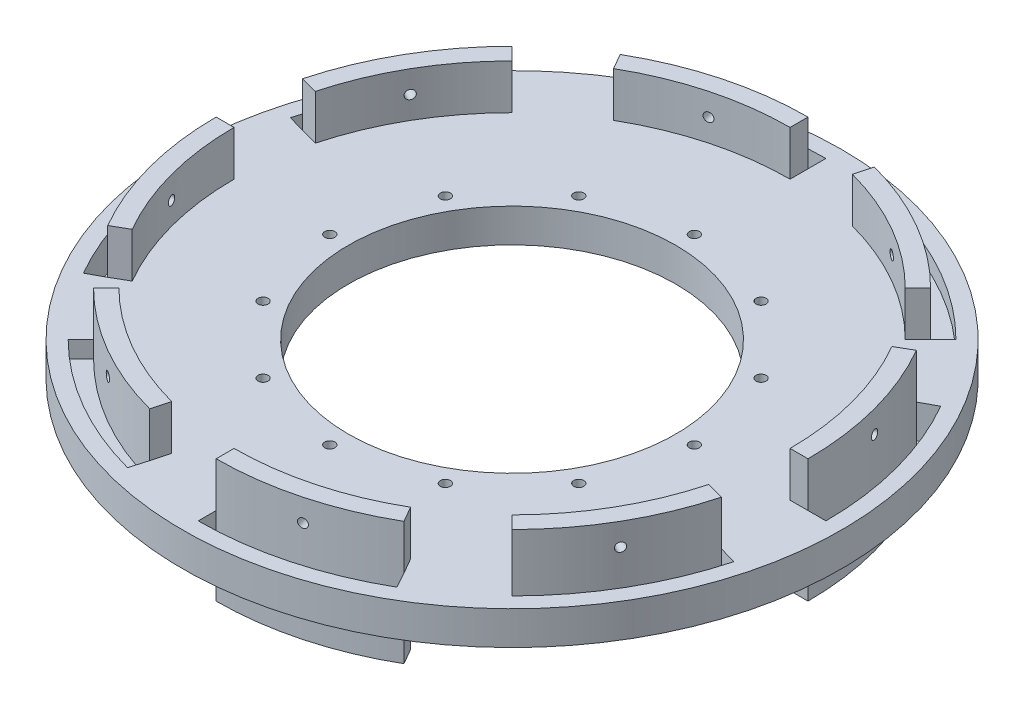
SolidWorks part; units mm, degrees
material "6061-T6 (SS)"
ref_plane "Front Plane" through (0, 0, 0) normal (0, 0, 1) x (1, 0, 0)
ref_plane "Top Plane" through (0, 0, 0) normal (0, 1, 0) x (1, 0, 0)
ref_plane "Right Plane" through (0, 0, 0) normal (1, 0, 0) x (0, 0, -1)
sketch "Sketch1" plane through (0, 0, 0) normal (0, 1, 0) x (1, 0, 0)
  line L5 (0, 0) -> (127.635, 0)
  line L6 (0, 0) -> (0, 127.635)
  line L7 (0, 127.635) -> (127.635, 127.635)
  line L8 (127.635, 0) -> (127.635, 127.635)
  dimension "D1" = 127.635
  dimension "D2" = 127.635
extrude "Boss-Extrude1" add sketch "Sketch1" along normal blind 9.525 contours L5 L8 L7 L6
sketch "Sketch12" plane through (0, 0, 0) normal (0, -1, 0) x (1, 0, 0)
  line L0 (63.8175, 0) -> (63.8175, -127.635) construction
  line L1 (0, 0) -> (127.635, 0) construction
  line L2 (0, -127.635) -> (127.635, -127.635) construction
  line L3 (0, -63.8175) -> (127.635, -63.8175) construction
  line L4 (0, 0) -> (0, -127.635) construction
  line L5 (127.635, 0) -> (127.635, -127.635) construction
  circle A0 centre (63.8175, -63.8175) radius 93.345
  dimension "D1" = 186.69
extrude "Boss-Extrude2" add sketch "Sketch12" against normal up to surface (9.525 mm away) contours A0 up to face at (63.8175, 9.525, -63.8175)
sketch "Sketch5" plane through (0, 9.525, 0) normal (0, 1, 0) x (1, 0, 0)
  circle A0 centre (63.8175, 63.8175) radius 46.355
  circle A3 centre (63.8175, 63.8175) radius 93.345 construction
  dimension "D1" = 92.71
extrude "Cut-Extrude1" cut sketch "Sketch5" against normal blind 9.525
sketch "Sketch11" plane through (0, 9.525, 0) normal (0, 1, 0) x (1, 0, 0)
  line L0 (63.8175, 63.8175) -> (63.8175, 115.443) construction
  circle A0 centre (63.8175, 115.443) radius 1.4351
  dimension "D2" = 2.8702
  dimension "D1" = 51.6255
extrude "Cut-Extrude3" cut sketch "Sketch11" against normal through all contours A0
pattern_circular "CirPattern1" count 12 over 360 about axis through (63.8175, 9.525, -63.8175) along (0, 1, 0) of "Cut-Extrude3"
sketch "Sketch14" plane through (0, 9.525, 0) normal (0, -1, 0) x (1, 0, 0)
  line L0 (63.8175, -63.8175) -> (147.6375, -63.8175) construction
  line L1 (0, -5.2388) -> (0, 5.2388) construction
  line L2 (147.6375, -63.8175) -> (152.7175, -63.8175)
  line L3 (136.3808, -105.7742) -> (140.8401, -108.2104)
  circle A0 centre (63.8175, -63.8175) radius 46.355 construction
  arc A2 (147.6375, -63.8175) -> (136.3808, -105.7742) centre (63.8175, -63.8175) cw
  arc A3 (152.7175, -63.8175) -> (140.8401, -108.2104) centre (63.8175, -63.8175) cw
  point P0 (63.8175, -63.8175)
  dimension "D1" = 83.82
  dimension "D2" = 88.9
  dimension "D3" = 46.482
  dimension "D4" = 43.942
extrude "Bottom support hole" cut sketch "Sketch14" along normal blind 4.7625
sketch "Sketch15" plane through (0, 9.525, 0) normal (0, -1, 0) x (1, 0, 0)
  line L0 (63.8175, -63.8175) -> (147.6375, -63.8175) construction
  line L2 (142.5575, -63.8175) -> (147.6375, -63.8175)
  line L3 (131.983, -103.2314) -> (136.3808, -105.7742)
  arc A2 (142.5575, -63.8175) -> (131.983, -103.2314) centre (63.8175, -63.8175) cw
  arc A3 (147.6375, -63.8175) -> (136.3808, -105.7742) centre (63.8175, -63.8175) cw
  dimension "D1" = 43.942
  dimension "D3" = 78.74
extrude "Bottom support guide" add sketch "Sketch15" against normal blind 12.7
ref_plane "Bottom support bolt hole plane" through (153.6961, 0, -41.2358) normal (0.9658, 0, -0.2591) x (-0.2591, 0, -0.9658)
sketch "Sketch16" plane through (153.6961, 0, -41.2358) normal (0.9658, 0, -0.2591) x (-0.2591, 0, -0.9658)
  circle A0 centre (45.1039, 15.875) radius 1.27
  dimension "D1" = 2.54
  dimension "D2" = 21.717
  dimension "D3" = 6.35
extrude "Bottom support bolt hole" cut sketch "Sketch16" against normal blind 12.7 and the other way blind 12.7
ref_plane "Support mirror reference plane" through (0, 4.7625, 0) normal (0, 1, 0) x (1, 0, 0)
mirror "Support mirror" about plane through (0, 4.7625, 0) normal (0, 1, 0) of "Bottom support guide", "Bottom support bolt hole", "Bottom support hole"
pattern_circular "Support pattern" count 4 over 360 about axis through (63.8175, 9.525, -63.8175) along (0, 1, 0) of "Support mirror", "Bottom support bolt hole", "Bottom support guide", "Bottom support hole"
sketch "Sketch25" plane through (0, 9.525, 0) normal (0, -1, 0) x (1, 0, 0)
  line L0 (63.8175, -63.8175) -> (123.0872, -4.5478) construction
  line L2 (123.0872, -4.5478) -> (126.6793, -0.9557)
  line L3 (144.7953, -42.1754) -> (149.6712, -40.7448)
  line L5 (63.8175, -63.8175) -> (147.6375, -63.8175) construction
  arc A2 (123.0872, -4.5478) -> (144.7953, -42.1754) centre (63.8175, -63.8175) cw
  arc A3 (126.6793, -0.9557) -> (149.6712, -40.7448) centre (63.8175, -63.8175) cw
  point P0 (63.8175, -63.8175)
  dimension "D1" = 83.82
  dimension "D2" = 88.9
  dimension "D3" = 46.482
  dimension "D4" = 43.942
  dimension "D5" = 45
extrude "Top support hole" cut sketch "Sketch25" along normal blind 4.7625
sketch "Sketch27" plane through (-7.9384, 9.525, 69.1212) normal (0, -1, 0) x (1, 0, 0)
  line L0 (134.6177, -70.0769) -> (131.0256, -73.669) construction
  line L2 (131.0256, -73.669) -> (127.4335, -77.2611)
  line L3 (152.7338, -111.2966) -> (147.826, -112.6083)
  arc A2 (131.0256, -73.669) -> (152.7338, -111.2966) centre (71.7559, -132.9387) cw
  arc A3 (127.4335, -77.2611) -> (147.826, -112.6083) centre (71.7559, -132.9387) cw
  dimension "D1" = 78.74
extrude "Top support guide" add sketch "Sketch27" against normal blind 12.7
ref_plane "Top support bolt hole plane" through (90.3812, 0, 52.1428) normal (-0.8662, 0, -0.4997) x (-0.4997, 0, 0.8662)
sketch "Sketch29" plane through (90.3812, 0, 52.1428) normal (-0.8662, 0, -0.4997) x (-0.4997, 0, 0.8662)
  line L0 (-108.8891, 22.225) -> (-108.8891, 9.525) construction
  circle A0 centre (-87.1721, 15.875) radius 1.27
  dimension "D1" = 2.54
  dimension "D2" = 21.717
  dimension "D3" = 6.35
extrude "Top support bolt hole" cut sketch "Sketch29" against normal blind 12.7 and the other way blind 12.7
pattern_circular "CirPattern4" count 4 over 360 about axis through (63.8175, 0, -63.8175) along (0, -1, 0) of "Top support bolt hole", "Top support guide", "Top support hole", "Bottom support bolt hole", "Bottom support guide", "Bottom support hole"
